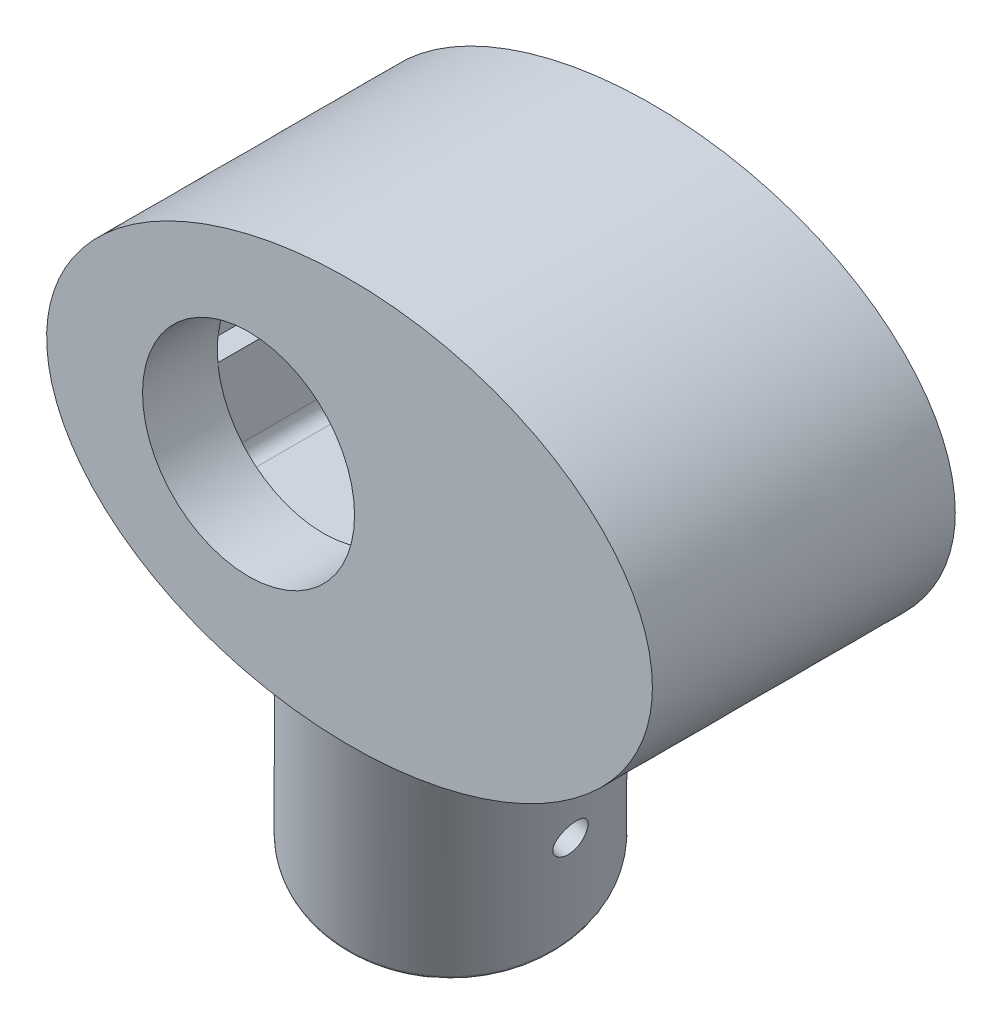
SolidWorks part; units mm, degrees
ref_plane "Front Plane" through (0, 0, 0) normal (0, 0, 1) x (1, 0, 0)
ref_plane "Top Plane" through (0, 0, 0) normal (0, 1, 0) x (1, 0, 0)
ref_plane "Right Plane" through (0, 0, 0) normal (1, 0, 0) x (0, 0, -1)
sketch "Sketch2" plane through (0, 0, 0) normal (0, 0, 1) x (1, 0, 0)
  line L102 (-3.3983, 10.2) -> (7.0395, 10.2) construction
  line L103 (7.0395, 10.2) -> (29.1, 10.2) construction
  line L104 (30.1, 9.2) -> (30.1, 0.75) construction
  line L105 (31.7, 0.75) -> (30.1, 0.75) construction
  line L106 (31.7, 0.75) -> (35.9, 0.75) construction
  line L107 (35.9, 0.75) -> (35.9, -0.75) construction
  line L108 (35.9, -0.75) -> (30.1, -0.75) construction
  line L109 (30.1, -0.75) -> (30.1, -9.2) construction
  line L110 (29.1, -10.2) -> (7.0395, -10.2) construction
  line L111 (7.0395, -10.2) -> (-3.3983, -10.2) construction
  line L112 (-3.3983, -10.2) -> (-9.1, -10.2) construction
  line L113 (-11.7, -0.75) -> (-10.1, -0.75) construction
  line L114 (-11.7, -0.75) -> (-15.9, -0.75) construction
  line L115 (-15.9, -0.75) -> (-15.9, 0.75) construction
  line L116 (-15.9, 0.75) -> (-11.7, 0.75) construction
  line L117 (-10.1, 0.75) -> (-11.7, 0.75) construction
  line L118 (-10.1, -9.2) -> (-10.1, -0.75) construction
  line L119 (-10.1, 0.75) -> (-10.1, 9.2) construction
  line L120 (-9.1, 10.2) -> (-3.3983, 10.2) construction
  line L121 (-3.3983, 10.6) -> (7.0395, 10.6)
  line L122 (7.0395, 10.6) -> (29.1, 10.6)
  line L123 (30.5, 9.2) -> (30.5, 1.15)
  line L124 (31.7, 1.15) -> (30.5, 1.15)
  line L125 (31.7, 1.15) -> (36.3, 1.15)
  line L126 (36.3, 1.15) -> (36.3, -1.15)
  line L127 (36.3, -1.15) -> (30.5, -1.15)
  line L128 (30.5, -1.15) -> (30.5, -9.2)
  line L129 (29.1, -10.6) -> (7.0395, -10.6)
  line L130 (7.0395, -10.6) -> (-3.3983, -10.6)
  line L131 (-3.3983, -10.6) -> (-9.1, -10.6)
  line L132 (-10.5, -9.2) -> (-10.5, -1.15)
  line L133 (-11.7, -1.15) -> (-10.5, -1.15)
  line L134 (-11.7, -1.15) -> (-16.3, -1.15)
  line L135 (-16.3, -1.15) -> (-16.3, 1.15)
  line L136 (-16.3, 1.15) -> (-11.7, 1.15)
  line L137 (-10.5, 1.15) -> (-11.7, 1.15)
  line L138 (-10.5, 1.15) -> (-10.5, 9.2)
  line L139 (-9.1, 10.6) -> (-3.3983, 10.6)
  arc A20 (30.1, 9.2) -> (29.1, 10.2) centre (29.1, 9.2) ccw construction
  arc A21 (29.1, -10.2) -> (30.1, -9.2) centre (29.1, -9.2) ccw construction
  arc A22 (-10.1, -9.2) -> (-9.1, -10.2) centre (-9.1, -9.2) ccw construction
  arc A23 (-9.1, 10.2) -> (-10.1, 9.2) centre (-9.1, 9.2) ccw construction
  arc A24 (30.5, 9.2) -> (29.1, 10.6) centre (29.1, 9.2) ccw
  arc A25 (29.1, -10.6) -> (30.5, -9.2) centre (29.1, -9.2) ccw
  arc A26 (-10.5, -9.2) -> (-9.1, -10.6) centre (-9.1, -9.2) ccw
  arc A27 (-9.1, 10.6) -> (-10.5, 9.2) centre (-9.1, 9.2) ccw
  ellipse E0 centre (10, 0) end of major axis (40, 0) minor radius 20
  dimension "D2" = 60
  dimension "D3" = 40
  dimension "D4" = 10
  dimension "D1" = 0.4
extrude "Boss-Extrude1" add sketch "Sketch2" along normal blind 30 contours E0 region at (-19.2789, -0.0201, 0)
sketch "Sketch3" plane through (0, 0, 0) normal (0, 0, -1) x (-1, 0, 0)
  arc A0 (-36.8729, -5.875) -> (-36.8729, -4.125) centre (-34.8, -5) ccw construction
  arc A1 (-36.8729, 4.125) -> (-36.8729, 5.875) centre (-34.8, 5) ccw construction
  arc A2 (16.8729, 5.875) -> (16.8729, 4.125) centre (14.8, 5) ccw construction
  arc A3 (16.8729, -4.125) -> (16.8729, -5.875) centre (14.8, -5) ccw construction
  arc A4 (-36.8729, -5.875) -> (-36.8729, -4.125) centre (-34.8, -5) ccw construction
  arc A5 (-36.8729, 4.125) -> (-36.8729, 5.875) centre (-34.8, 5) ccw construction
  arc A6 (16.8729, 5.875) -> (16.8729, 4.125) centre (14.8, 5) ccw construction
  arc A7 (16.8729, -4.125) -> (16.8729, -5.875) centre (14.8, -5) ccw construction
  arc A8 (16.8729, -5.875) -> (16.8729, -4.125) centre (14.8, -5) ccw construction
  arc A9 (16.8729, 4.125) -> (16.8729, 5.875) centre (14.8, 5) ccw construction
  arc A10 (-36.8729, 5.875) -> (-36.8729, 4.125) centre (-34.8, 5) ccw construction
  arc A11 (-36.8729, -4.125) -> (-36.8729, -5.875) centre (-34.8, -5) ccw construction
  arc A12 (-35.9516, -5.4861) -> (-35.9516, -4.5139) centre (-34.8, -5) ccw
  arc A13 (-35.9516, -4.5139) -> (-35.9516, -5.4861) centre (-34.8, -5) ccw
  arc A14 (-35.9516, 4.5139) -> (-35.9516, 5.4861) centre (-34.8, 5) ccw
  arc A15 (-35.9516, 5.4861) -> (-35.9516, 4.5139) centre (-34.8, 5) ccw
  arc A16 (15.9516, 5.4861) -> (15.9516, 4.5139) centre (14.8, 5) ccw
  arc A17 (15.9516, 4.5139) -> (15.9516, 5.4861) centre (14.8, 5) ccw
  arc A18 (15.9516, -4.5139) -> (15.9516, -5.4861) centre (14.8, -5) ccw
  arc A19 (15.9516, -5.4861) -> (15.9516, -4.5139) centre (14.8, -5) ccw
  dimension "D1" = 1.25
  dimension "D2" = 3.85
  dimension "D3" = 1.5
extrude "Cut-Extrude1" cut sketch "Sketch3" against normal blind 3
ref_plane "Plane3" through (10, 0, 0) normal (1, 0, 0) x (0, 0, -1)
sketch "Sketch16" [suppressed] plane through (10, 0, 0) normal (1, 0, 0) x (0, 0, -1)
  line L0 (0, 0) -> (50000, 0) construction
ref_plane "Plane6" [suppressed] through (9.648, 1.8427, 0) normal (-0.9822, -0.1876, 0) x (0, 0, -1)
sketch "Sketch6" plane through (11.1721, -6.137, 0) normal (-0.9822, -0.1876, 0) x (-0.1876, 0.9822, 0)
  line L1 (26.6831, 0) -> (-14.1873, 0) construction
  line L3 (-14.1873, -30) -> (26.6831, -30) construction
  line L7 (26.6831, -15) -> (51.6831, -15)
  line L8 (26.6831, 0) -> (-14.1873, 0) construction
  line L9 (-14.1873, -30) -> (26.6831, -30) construction
  line L10 (26.6831, 0) -> (26.6831, -30) construction
  dimension "D1" = 25
ref_plane "Plane1" through (1.4762, 44.6285, 15) normal (-0.1876, 0.9822, 0) x (0.9822, 0.1876, 0)
sketch "Sketch7" plane through (1.4762, 44.6285, 15) normal (-0.1876, 0.9822, 0) x (0.9822, 0.1876, 0)
  circle A0 centre (0, 0) radius 10.35
  circle A1 centre (0, 0) radius 12.35
  point P12 (0, 0)
  dimension "D1" = 20.7
  dimension "D2" = 2
extrude "Boss-Extrude2" [suppressed] add sketch "Sketch7" against normal up to body
sketch "Sketch8" plane through (0, 0, 30) normal (0, 0, 1) x (1, 0, 0)
  line L0 (10, 0) -> (10, -3.4904) construction
  ellipse E0 centre (10, 0) end of major axis (40, 0) minor radius 20 construction
  ellipse E1 centre (10, 0) end of major axis (40, 0) minor radius 20
extrude "Boss-Extrude4" add sketch "Sketch8" against normal up to surface (7.4 mm away)
sketch "Sketch12" [suppressed] plane through (10, -10, 0) normal (-1, 0, 0) x (0, 1, 0)
  line L6 (30, -30) -> (30, 0) construction
  line L7 (30, -15) -> (52.3116, -15) construction
  circle A0 centre (41.1558, -15) radius 1.7
  ellipse E0 centre (54.6285, -15) end of major axis (54.6285, -27.35) minor radius 2.3169 construction
  dimension "D1" = 3.4
extrude "Cut-Extrude3" [suppressed] cut sketch "Sketch12" against normal through all both and the other way through all
sketch "Sketch15" plane through (10, 0, 0) normal (1, 0, 0) x (0, 0, -1)
  line L0 (0, 0) -> (50000, 0) construction
  line L1 (0, -20) -> (0, 20) construction
  point P4 (0, 0)
ref_plane "Plane4" through (9.4211, -2.3354, 0) normal (0.9706, -0.2406, 0) x (0, 0, -1)
sketch "Sketch9" plane through (12.5635, 10.3412, 0) normal (0.9706, -0.2406, 0) x (-0.2406, -0.9706, 0)
  line L0 (31.3652, -30) -> (31.3652, 0) construction
  line L1 (31.3652, -30) -> (31.3652, 0) construction
  line L2 (31.3652, -15) -> (55.6745, -9.1639)
  dimension "D1" = 25
  dimension "D2" = 13.5
ref_plane "Plane2" through (-0.8323, -43.6977, 9.1639) normal (-0.234, -0.9438, -0.2334) x (-0.4258, 0.3153, -0.8481)
sketch "Sketch10" plane through (-0.8323, -43.6977, 9.1639) normal (-0.234, -0.9438, -0.2334) x (-0.4258, 0.3153, -0.8481)
  line L0 (-12.7213, -7.1349) -> (12.7213, 7.1349) construction
  circle A0 centre (0, 0) radius 10.35
  circle A1 centre (0, 0) radius 12.35
  dimension "D1" = 20.7
  dimension "D2" = 2
extrude "Boss-Extrude5" add sketch "Sketch10" against normal up to surface (28.1469 mm away) up to face at (40, 0, 30)
sketch "Sketch11" plane through (12.5635, 10.3412, 0) normal (0.9706, -0.2406, 0) x (-0.2406, -0.9706, 0)
  line L2 (31.3652, 0) -> (31.3652, -30) construction
  line L3 (31.3652, -15) -> (55.6745, -9.1639) construction
  line L4 (58.0906, -19.2279) -> (53.2583, 0.9002) construction
  circle A1 centre (43.5198, -12.0819) radius 1.7
  dimension "D1" = 3.4
extrude "Cut-Extrude2" cut sketch "Sketch11" against normal through all both and the other way through all
sketch "Sketch13" plane through (0, 0, 30) normal (0, 0, 1) x (1, 0, 0)
  circle A0 centre (0, 0) radius 10.5
  dimension "D1" = 21
extrude "Cut-Extrude4" cut sketch "Sketch13" against normal through all both and the other way through all
sketch "Sketch14" plane through (0, 0, 30) normal (0, 0, 1) x (1, 0, 0)
  circle A1 centre (20, 0) radius 4
  ellipse E3 centre (10, 0) end of major axis (40, 0) minor radius 20
  ellipse E4 centre (10, 0) end of major axis (40, 0) minor radius 20
  dimension "D1" = 8
  dimension "D3" = 10
  dimension "D2" = 0
extrude "Cut-Extrude5" [suppressed] cut sketch "Sketch14" against normal through all both and the other way through all contours A1
ref_plane "Plane5" [suppressed] through (-25, 0, 0) normal (1, 0, 0) x (0, 0, -1)
mirror "Mirror1" [suppressed] about plane through (-25, 0, 0) normal (1, 0, 0) of bodies 112 113
delete or keep bodies "Body-Delete/Keep 1" [suppressed] type delete bodies bodies 112
fillet "Fillet1" radius 0.5 2 edges at (11.1549, -46.6692, 9.1639) (9.2136, -46.188, 9.1639)
fillet "Fillet2" [suppressed] radius 0.5
fillet "Fillet3" [suppressed] radius 0.5
fillet "Fillet4" [suppressed] radius 0.5
